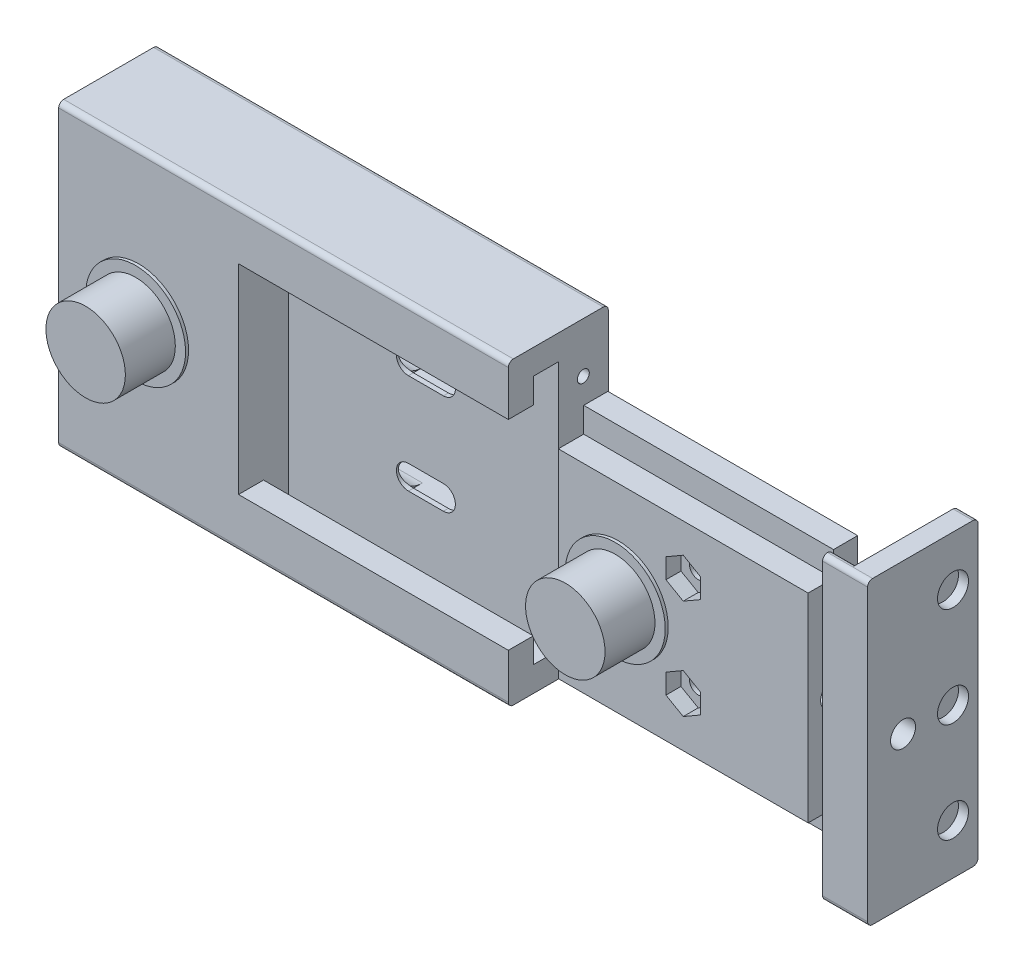
SolidWorks part; units mm, degrees
other "Slider"
other "Frame"
other "Cover"
ref_plane "Front Plane" through (0, 0, 0) normal (0, 0, 1) x (1, 0, 0)
ref_plane "Top Plane" through (0, 0, 0) normal (0, 1, 0) x (1, 0, 0)
ref_plane "Right Plane" through (0, 0, 0) normal (1, 0, 0) x (0, 0, -1)
sketch "Sketch1" plane through (0, 0, 0) normal (0, 0, 1) x (1, 0, 0)
  line L1 (-45, 30) -> (45, 30)
  line L2 (-45, 30) -> (-45, -30)
  line L3 (-45, -30) -> (45, -30)
  line L4 (45, 30) -> (45, -30)
  line L5 (-45, 30) -> (45, -30) construction
  line L6 (-45, -30) -> (45, 30) construction
  point P0 (0, 0)
  dimension "D1" = 90
  dimension "D2" = 60
extrude "Boss-Extrude1" add sketch "Sketch1" along normal blind 20
sketch "Sketch2" plane through (0, 0, 20) normal (0, 0, 1) x (1, 0, 0)
  line L0 (-45, 30) -> (-45, -30) construction
  circle A0 centre (-29, 0) radius 10
  dimension "D1" = 20
  dimension "D2" = 16
extrude "Boss-Extrude2" add sketch "Sketch2" along normal blind 0.6
sketch "Sketch3" plane through (0, 0, 20.6) normal (0, 0, 1) x (1, 0, 0)
  circle A0 centre (-29, 0) radius 7.95
  dimension "D1" = 15.9
extrude "Boss-Extrude3" add sketch "Sketch3" along normal blind 10
sketch "Sketch6" plane through (45, 0, 0) normal (1, 0, 0) x (0, 0, -1)
  line L0 (-20, 20) -> (-15, 20)
  line L2 (-20, -30) -> (-20, 30) construction
  line L4 (-15, 20) -> (-15, 25)
  line L5 (-15, 25) -> (-10, 25)
  line L6 (-10, 25) -> (-10, -25)
  line L7 (-10, -25) -> (-15, -25)
  line L8 (-15, -25) -> (-15, -20)
  line L9 (-15, -20) -> (-20, -20)
  line L10 (-20, -20) -> (-20, 20)
  line L11 (-20, 30) -> (0, 30) construction
  point P4 (-10, 30)
  point P5 (-10, 0)
  point P13 (-20, 0)
  dimension "D1" = 10
extrude "Cut-Extrude2" cut sketch "Sketch6" against normal blind 54
sketch "Sketch14" plane through (0, 0, 0) normal (0, 0, -1) x (-1, 0, 0)
  line L7 (9, 0) -> (45, 0) construction
  line L8 (45, 30) -> (45, -30) construction
  line L9 (9, 20) -> (-45, 20) construction
  line L10 (9, -20) -> (-45, -20) construction
  line L11 (9, 20) -> (-45, 20) construction
  line L12 (9, -20) -> (-45, -20) construction
  line L13 (9, 20) -> (9, 0) construction
  line L14 (9, 0) -> (9, -20) construction
  circle A0 centre (27, 10) radius 1.75
  circle A1 centre (27, -10) radius 1.75
  point P13 (27, 0)
  point P14 (9, 10)
  point P15 (9, -10)
  dimension "D1" = 3.5
extrude "Cut-Extrude4" cut sketch "Sketch14" against normal blind 18
ref_plane "Plane1" through (55, 0, 0) normal (1, 0, 0) x (0, 0, -1)
sketch "Sketch7" plane through (55, 0, 0) normal (1, 0, 0) x (0, 0, -1)
  line L1 (-20, -19.92) -> (-14.92, -19.92)
  line L2 (-14.92, -19.92) -> (-14.92, -24.92)
  line L3 (-14.92, -24.92) -> (-10.08, -24.92)
  line L4 (-10.08, -24.92) -> (-10.08, 24.92)
  line L5 (-10.08, 24.92) -> (-14.92, 24.92)
  line L6 (-14.92, 24.92) -> (-14.92, 19.92)
  line L7 (-14.92, 19.92) -> (-20, 19.92)
  line L8 (-20, 20) -> (-20, -20)
  line L9 (-20, -20) -> (-15, -20)
  line L10 (-15, -20) -> (-15, -25)
  line L11 (-15, -25) -> (-10, -25)
  line L12 (-10, -25) -> (-10, 25)
  line L13 (-10, 25) -> (-15, 25)
  line L14 (-15, 25) -> (-15, 20)
  line L15 (-15, 20) -> (-20, 20)
  line L16 (-20, 20) -> (-20, -20) construction
  line L17 (-20, -20) -> (-15, -20) construction
  line L18 (-15, -20) -> (-15, -25) construction
  line L19 (-15, -25) -> (-10, -25) construction
  line L20 (-10, -25) -> (-10, 25) construction
  line L21 (-10, 25) -> (-15, 25) construction
  line L22 (-15, 25) -> (-15, 20) construction
  line L23 (-15, 20) -> (-20, 20) construction
  line L24 (-14.92, 19.92) -> (-19.92, 19.92) construction
  line L25 (-19.92, -19.92) -> (-14.92, -19.92) construction
  line L26 (-20, -19.92) -> (-20, 19.92)
  line L32 (-19.92, 19.92) -> (-19.92, -19.92) construction
  dimension "D1" = 0
  dimension "D2" = 0.08
extrude "Boss-Extrude4" add sketch "Sketch7" along normal blind 50 separate body
sketch "Sketch10" plane through (0, 0, 20) normal (0, 0, 1) x (1, 0, 0)
  line L0 (55, 19.92) -> (55, -19.92) construction
  circle A0 centre (67, 0) radius 10
  dimension "D1" = 20
  dimension "D2" = 12
extrude "Boss-Extrude5" add sketch "Sketch10" along normal blind 0.6
sketch "Sketch11" plane through (0, 0, 20.6) normal (0, 0, 1) x (1, 0, 0)
  circle A0 centre (67, 0) radius 7.95
  dimension "D1" = 15.9
extrude "Boss-Extrude6" add sketch "Sketch11" along normal blind 10
sketch "Sketch16" plane through (0, 0, 10.08) normal (0, 0, -1) x (-1, 0, 0)
  line L0 (9, 20) -> (-45, 20) construction
  line L1 (9, -20) -> (-45, -20) construction
  line L2 (9, 20) -> (-118.7284, 20) construction
  line L3 (9, -20) -> (-118.7284, -20) construction
  line L4 (-105, 0) -> (-55, 0) construction
  line L5 (-105, -24.92) -> (-105, 24.92) construction
  line L6 (-55, -24.92) -> (-55, 24.92) construction
  line L7 (-105, 20) -> (-105, 0) construction
  line L8 (-105, 0) -> (-105, -20) construction
  circle A0 centre (-80, 10) radius 1.75
  circle A1 centre (-80, -10) radius 1.75
  point P19 (-80, 0)
  point P20 (-105, -10)
  point P21 (-105, 10)
  dimension "D1" = 3.5
extrude "Cut-Extrude5" cut sketch "Sketch16" against normal up to surface (9.92 mm away) up to face at (77, 0, 20)
sketch "Sketch17" plane through (0, 0, 20) normal (0, 0, 1) x (1, 0, 0)
  line L1 (80, -6.0163) -> (76.55, -8.0081)
  line L2 (76.55, -8.0081) -> (76.55, -11.9919)
  line L3 (76.55, -11.9919) -> (80, -13.9837)
  line L4 (80, -13.9837) -> (83.45, -11.9919)
  line L5 (83.45, -11.9919) -> (83.45, -8.0081)
  line L6 (83.45, -8.0081) -> (80, -6.0163)
  line L7 (80, 13.9837) -> (76.55, 11.9919)
  line L8 (76.55, 11.9919) -> (76.55, 8.0081)
  line L9 (76.55, 8.0081) -> (80, 6.0163)
  line L10 (80, 6.0163) -> (83.45, 8.0081)
  line L11 (83.45, 8.0081) -> (83.45, 11.9919)
  line L12 (83.45, 11.9919) -> (80, 13.9837)
  circle A0 centre (80, -10) radius 3.45 construction
  circle A1 centre (80, 10) radius 3.45 construction
  dimension "D1" = 6.9
extrude "Cut-Extrude6" cut sketch "Sketch17" against normal blind 3
ref_plane "Plane2" through (-33, 0, 0) normal (-1, 0, 0) x (0, 0, 1)
sketch "Sketch20" plane through (-33, 0, 0) normal (-1, 0, 0) x (0, 0, 1)
  line L0 (15, 20) -> (20, 20) construction
  line L1 (20, 20) -> (20, -20) construction
  line L2 (15, 20) -> (20, 20)
  line L3 (20, 20) -> (20, -20)
  line L4 (20, -20) -> (15, -20) construction
  line L5 (20, -20) -> (15, -20)
  line L6 (15, 20) -> (15, 0) construction
  line L7 (15, 0) -> (15, -20) construction
  line L8 (0, 30) -> (0, -30) construction
  line L9 (4.8, 14.8) -> (0, 14.8)
  line L10 (0, 14.8) -> (0, 5.2)
  line L11 (0, 5.2) -> (4.8, 5.2)
  line L12 (4.8, -5.2) -> (0, -5.2)
  line L13 (0, -5.2) -> (0, -14.8)
  line L14 (0, -14.8) -> (4.8, -14.8)
  arc A0 (4.8, 5.2) -> (4.8, 14.8) centre (4.8, 10) ccw
  arc A1 (4.8, -14.8) -> (4.8, -5.2) centre (4.8, -10) ccw
  point P8 (15, 10)
  point P12 (15, -10)
  dimension "D1" = 9.6
extrude "Cut-Extrude8" cut sketch "Sketch20" against normal blind 62 contours L11 A0 L9 L10 | L14 A1 L12 L13 region at (-33, 10, 4.3519) region at (-33, -10, 4.3519)
sketch "Sketch22" plane through (0, 0, 0) normal (0, 0, -1) x (-1, 0, 0)
  line L0 (33, 14.8) -> (33, 5.2) construction
  line L1 (33, -5.2) -> (33, -14.8) construction
  line L2 (-22, 12.4) -> (-15, 12.4)
  line L3 (-15, 7.6) -> (-22, 7.6)
  line L4 (-22, -7.6) -> (-15, -7.6)
  line L5 (-15, -12.4) -> (-22, -12.4)
  line L6 (9, -25) -> (9, 25) construction
  arc A0 (-22, 12.4) -> (-22, 7.6) centre (-22, 10) ccw
  arc A1 (-22, -7.6) -> (-22, -12.4) centre (-22, -10) ccw
  arc A2 (-15, 7.6) -> (-15, 12.4) centre (-15, 10) ccw
  arc A3 (-15, -12.4) -> (-15, -7.6) centre (-15, -10) ccw
  point P7 (33, 10)
  point P10 (33, -10)
  dimension "D1" = 4.8
  dimension "D2" = 24
  dimension "D3" = 7
extrude "Cut-Extrude9" cut sketch "Sketch22" against normal up to surface (10 mm away) up to face at (18, 0, 10)
sketch "Sketch24" plane through (0, 0, 0) normal (0, 0, -1) x (-1, 0, 0)
  line L0 (-29, 5.2) -> (33, 5.2) construction
  line L1 (-29, 14.8) -> (-12.6, 14.8)
  line L2 (-29, 14.8) -> (-29, 5.2)
  line L3 (-29, 5.2) -> (-12.6, 5.2)
  line L4 (-12.6, 14.8) -> (-12.6, 5.2)
  line L5 (-29, 14.8) -> (-12.6, 5.2) construction
  line L6 (-29, 5.2) -> (-12.6, 14.8) construction
  line L7 (-29, 14.8) -> (33, 14.8) construction
  line L8 (-29, 14.8) -> (-29, 5.2) construction
  line L9 (-29, -5.2) -> (33, -5.2) construction
  line L10 (-29, -5.2) -> (-12.6, -5.2)
  line L11 (-29, -5.2) -> (-29, -14.8)
  line L12 (-29, -14.8) -> (-12.6, -14.8)
  line L13 (-12.6, -5.2) -> (-12.6, -14.8)
  line L14 (-29, -5.2) -> (-12.6, -14.8) construction
  line L15 (-29, -14.8) -> (-12.6, -5.2) construction
  line L16 (-29, -5.2) -> (-29, -14.8) construction
  line L17 (-29, -14.8) -> (33, -14.8) construction
  line L18 (21, 5.2) -> (33, 14.8) construction
  line L19 (33, 14.8) -> (21, 14.8)
  line L20 (33, 14.8) -> (33, 5.2)
  line L21 (33, 5.2) -> (21, 5.2)
  line L22 (21, 14.8) -> (21, 5.2)
  line L23 (33, -5.2) -> (21, -5.2)
  line L24 (33, -5.2) -> (33, -14.8)
  line L25 (33, -14.8) -> (21, -14.8)
  line L26 (21, -5.2) -> (21, -14.8)
  line L27 (21, -14.8) -> (33, -5.2) construction
  arc A0 (-15, 7.6) -> (-15, 12.4) centre (-15, 10) ccw construction
  circle A2 centre (27, 10) radius 1.75 construction
  point P0 (-20.8, 10)
  point P11 (-20.8, -10)
  point P36 (27, 10)
extrude "Cut-Extrude10" cut sketch "Sketch24" against normal blind 9
fillet "Fillet1" radius 0.8 12 edges at (-21, -14.8, 6.9) (-21, -13.5619, 9) (-27, -14.8, 9) (-27, 5.2, 9) (-21, 5.2, 6.9) (-27, -5.2, 9) (-21, -5.2, 6.9) (-21, -6.4381, 9) (-21, 6.4381, 9) (-27, 14.8, 9) (-21, 14.8, 6.9) (-21, 13.5619, 9)
sketch "Sketch26" plane through (0, 0, 18) normal (0, 0, -1) x (-1, 0, 0)
  line L1 (23.0163, 10) -> (25.0081, 6.55)
  line L2 (25.0081, 6.55) -> (28.9919, 6.55)
  line L3 (28.9919, 6.55) -> (30.9837, 10)
  line L4 (30.9837, 10) -> (28.9919, 13.45)
  line L5 (28.9919, 13.45) -> (25.0081, 13.45)
  line L6 (25.0081, 13.45) -> (23.0163, 10)
  line L7 (23.0163, -10) -> (25.0081, -13.45)
  line L8 (25.0081, -13.45) -> (28.9919, -13.45)
  line L9 (28.9919, -13.45) -> (30.9837, -10)
  line L10 (30.9837, -10) -> (28.9919, -6.55)
  line L11 (28.9919, -6.55) -> (25.0081, -6.55)
  line L12 (25.0081, -6.55) -> (23.0163, -10)
  circle A0 centre (27, 10) radius 3.45 construction
  circle A1 centre (27, -10) radius 3.45 construction
  dimension "D1" = 6.9
extrude "Cut-Extrude11" cut sketch "Sketch26" along normal blind 3 contours L1 L2 L3 L4 L5 L6 | L7 L8 L9 L10 L11 L12
sketch "Sketch27" plane through (-45, 0, 0) normal (-1, 0, 0) x (0, 0, 1)
  line L0 (15, -13.45) -> (18, -13.45) construction
  line L1 (15, 6.55) -> (18, 6.55) construction
  line L2 (15, -6.55) -> (18, -6.55) construction
  line L3 (15, 13.45) -> (18, 13.45) construction
  line L4 (15, -13.45) -> (18, -13.45)
  line L5 (15, 6.55) -> (18, 6.55)
  line L6 (15, -6.55) -> (18, -6.55)
  line L7 (15, 13.45) -> (18, 13.45)
  line L8 (18, 13.45) -> (18, 6.55)
  line L9 (15, 6.55) -> (15, 13.45)
  line L10 (15, -6.55) -> (15, -13.45)
  line L11 (18, -13.45) -> (18, -6.55)
extrude "Cut-Extrude12" cut sketch "Sketch27" against normal up to vertex (16.0081 mm away) up to point (-28.9919, 6.55, 15)
sketch "Sketch28" plane through (45, 0, 0) normal (1, 0, 0) x (0, 0, -1)
  line L1 (-15, 20) -> (-20, 20) construction
  line L2 (-20, -20) -> (-15, -20) construction
  line L3 (-10, 25) -> (0, 25) construction
  line L4 (0, -30) -> (0, 30) construction
  circle A0 centre (-5, 20) radius 1.2
  circle A1 centre (-5, 0) radius 1.2
  circle A2 centre (-5, -20) radius 1.2
  point P8 (-5, 25)
  dimension "D1" = 2.4
extrude "Cut-Extrude13" cut sketch "Sketch28" against normal blind 15
sketch "Sketch29" plane through (105, 0, 0) normal (1, 0, 0) x (0, 0, -1)
  line L0 (-15, 25) -> (-15, 20) construction
  circle A0 centre (-15, 0) radius 2.5
  dimension "D1" = 5
extrude "Cut-Extrude14" cut sketch "Sketch29" against normal blind 40
ref_plane "Plane3" through (75, 0, 0) normal (1, 0, 0) x (0, 0, -1)
sketch "Sketch30" plane through (75, 0, 0) normal (1, 0, 0) x (0, 0, -1)
  line L0 (-12.7195, 3.95) -> (-10.08, 3.95)
  line L1 (-10.4389, 0) -> (-12.7195, 3.95) construction
  line L2 (-12.7195, 3.95) -> (-17.2805, 3.95)
  line L3 (-17.2805, 3.95) -> (-19.5611, 0)
  line L4 (-19.5611, 0) -> (-17.2805, -3.95)
  line L5 (-17.2805, -3.95) -> (-12.7195, -3.95)
  line L6 (-12.7195, -3.95) -> (-10.4389, 0) construction
  line L7 (-10.08, -24.92) -> (-10.08, 24.92) construction
  line L8 (-10.08, 3.95) -> (-10.08, -3.95)
  line L9 (-10.08, -3.95) -> (-12.7195, -3.95)
  circle A0 centre (-15, 0) radius 3.95 construction
  dimension "D1" = 7.9
extrude "Cut-Extrude15" cut sketch "Sketch30" against normal blind 3.4
ref_plane "Plane4" through (115, 0, 0) normal (1, 0, 0) x (0, 0, -1)
sketch "Sketch31" plane through (115, 0, 0) normal (1, 0, 0) x (0, 0, -1)
  line L0 (-20.1, 30) -> (-20.1, -30)
  line L12 (-20, 30) -> (-20, 20)
  line L13 (-20, 20) -> (-15, 20)
  line L14 (-15, 20) -> (-15, 25)
  line L15 (-15, 25) -> (-10, 25)
  line L16 (-10, 25) -> (-10, -25)
  line L17 (-10, -25) -> (-15, -25)
  line L18 (-15, -25) -> (-15, -20)
  line L19 (-15, -20) -> (-20, -20)
  line L20 (-20, -20) -> (-20, -30)
  line L21 (-20, -30) -> (0, -30)
  line L22 (0, -30) -> (0, 30)
  line L23 (0, 30) -> (-20, 30)
  line L24 (-20, 30) -> (-20, 20) construction
  line L32 (-20, -20) -> (-20, -30) construction
  line L33 (-20.1, -30) -> (0, -30)
  line L34 (0, -30) -> (0, 30)
  line L35 (0, 30) -> (-20.1, 30)
  circle A6 centre (-5, 20) radius 1.55
  circle A7 centre (-5, 0) radius 1.55
  circle A8 centre (-5, -20) radius 1.55
  circle A9 centre (-15, 0) radius 2.5 construction
  circle A10 centre (-15, 0) radius 2.5
  dimension "D3" = 3.1
  dimension "D2" = 0.1
  dimension "D1" = 0
extrude "Boss-Extrude7" add sketch "Sketch31" along normal blind 4 separate body
sketch "Sketch32" plane through (119, 0, 0) normal (1, 0, 0) x (0, 0, -1)
  circle A0 centre (-5, 20) radius 3.1
  circle A1 centre (-5, 0) radius 3.1
  circle A2 centre (-5, -20) radius 3.1
  dimension "D1" = 6.2
extrude "Cut-Extrude16" cut sketch "Sketch32" against normal blind 2
sketch "Sketch33" plane through (119, 0, 0) normal (1, 0, 0) x (0, 0, -1)
  line L0 (-20.1, 30) -> (-20.1, -30) construction
  line L1 (-20.1, 30) -> (-20.1, -30)
  line L2 (-20.1, 30) -> (-22.1, 30)
  line L3 (-22.1, 30) -> (-22.1, -30)
  line L4 (-22.1, -30) -> (-20.1, -30)
  dimension "D1" = 2
extrude "Boss-Extrude8" add sketch "Sketch33" against normal blind 9
fillet "Fillet2" radius 1 4 edges at (0, -30, 0) (0, -30, 20) (0, 30, 20) (0, 30, 0)
fillet "Fillet3" radius 1 6 edges at (112.5, -30, 20.1) (117, -30, 0) (114.5, -30, 22.1) (112.5, 30, 20.1) (114.5, 30, 22.1) (117, 30, 0)
sketch "Sketch34" plane through (117, 0, 0) normal (1, 0, 0) x (0, 0, -1)
  circle A0 centre (-5, -20) radius 1.55 construction
  circle A1 centre (-5, 0) radius 1.55 construction
  circle A2 centre (-5, 20) radius 1.55 construction
  circle A3 centre (-5, -20) radius 1.55
  circle A4 centre (-5, 0) radius 1.55
  circle A5 centre (-5, 20) radius 1.55
extrude "Boss-Extrude9" add sketch "Sketch34" against normal blind 0.6
